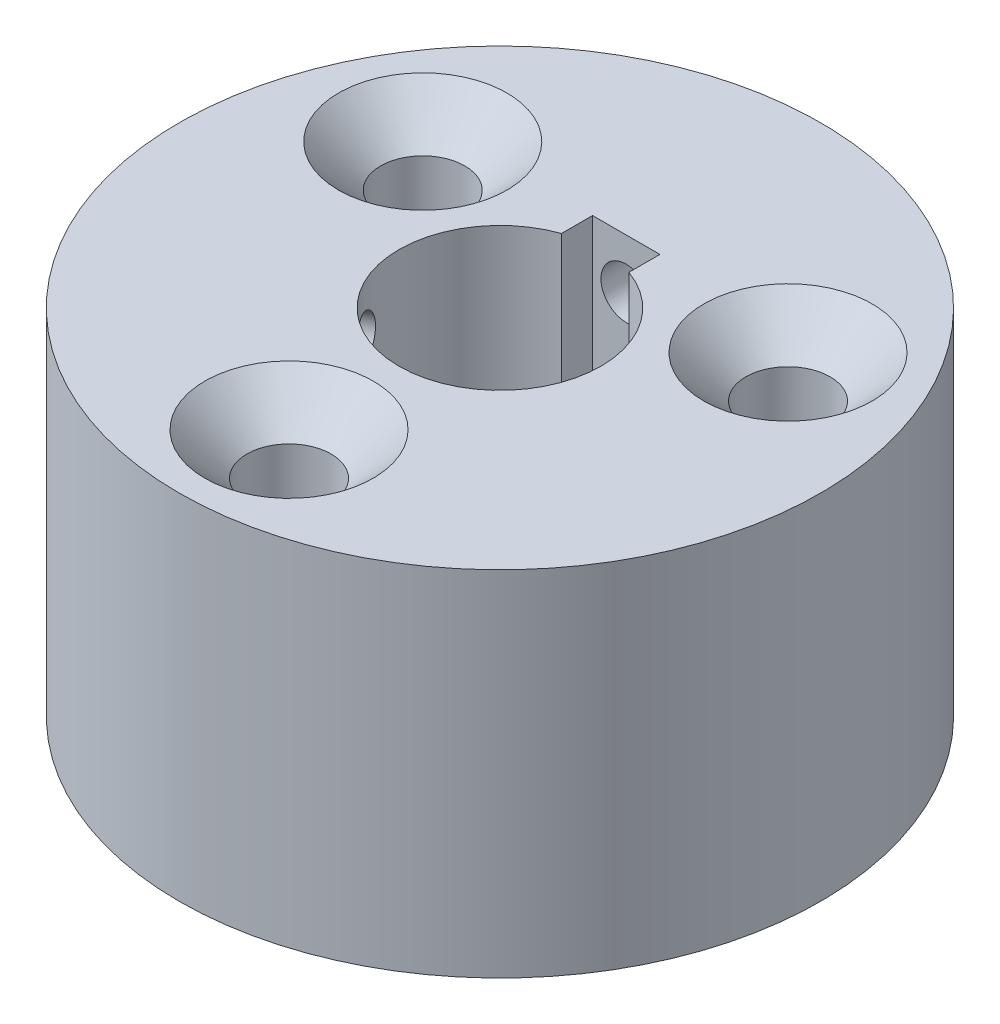
SolidWorks part; units mm, degrees
material "1060 Alloy"
ref_plane "Front Plane" through (0, 0, 0) normal (0, 0, 1) x (1, 0, 0)
ref_plane "Top Plane" through (0, 0, 0) normal (0, 1, 0) x (1, 0, 0)
ref_plane "Right Plane" through (0, 0, 0) normal (1, 0, 0) x (0, 0, -1)
sketch "Sketch1" plane through (0, 0, 0) normal (0, 1, 0) x (1, 0, 0)
  line L0 (0, 6) -> (0, 7.5) construction
  line L1 (-2, 7.5) -> (2, 7.5)
  line L2 (-2, 7.5) -> (-2, 5.6569)
  line L3 (2, 7.5) -> (2, 5.6569)
  line L4 (1, 7.5) -> (-1, 7.5)
  line L6 (0, 0) -> (-10.847, 6.2625) construction
  line L7 (0, 6) -> (0, -6) construction
  line L8 (0, -6) -> (0, -19.05) construction
  line L9 (0, 0) -> (10.847, 6.2625) construction
  circle A0 centre (0, 0) radius 19.05
  circle A1 centre (0, 0) radius 6
  circle A5 centre (0, -12.525) radius 2.5
  circle A6 centre (-10.847, 6.2625) radius 2.5
  circle A7 centre (10.847, 6.2625) radius 2.5
  point P9 (0, 7.5)
  point P16 (0, 7.5)
  dimension "D1" = 12
  dimension "D4" = 1
  dimension "D5" = 38.1
  dimension "D6" = 5
  dimension "D7" = 3
  dimension "D9" = 120
  dimension "D2" = 1.5
  dimension "D3" = 4
  dimension "D8" = 120
extrude "Boss-Extrude1" add sketch "Sketch1" along normal blind 21 contours A0 L3 A1 L2 region at (-18.5112, 0, 0)
sketch "Sketch2" plane through (0, 0, -7.5) normal (0, 0, 1) x (1, 0, 0)
  line L0 (0, 21) -> (0, 0) construction
  line L2 (-2, 21) -> (2, 21) construction
  circle A0 centre (0, 18) radius 1.5
  point P2 (0, 15)
  point P7 (0, 15)
  dimension "D2" = 3
  dimension "D1" = 3
extrude "Cut-Extrude1" cut sketch "Sketch2" against normal blind 15 and the other way blind 3
ref_plane "Plane1" through (0, 0, 0) normal (-0.866, 0, 0.5) x (0, -1, 0)
sketch "Sketch4" plane through (0, 0, 0) normal (-0.866, 0, 0.5) x (0, -1, 0)
  line L2 (0, 0) -> (-21, 0) construction
  line L3 (0, -19.05) -> (0, 19.05) construction
  line L4 (-21, 19.05) -> (-21, -19.05) construction
  circle A1 centre (-18, 0) radius 1.5
  dimension "D1" = 3
  dimension "D2" = 3
  dimension "D3" = 0
extrude "Cut-Extrude2" cut sketch "Sketch4" along normal blind 20
chamfer "Chamfer1" distance 2.5 angle 45 3 edges at (0, 21, 15.025) (-10.847, 21, -3.7625) (10.847, 21, -3.7625)
